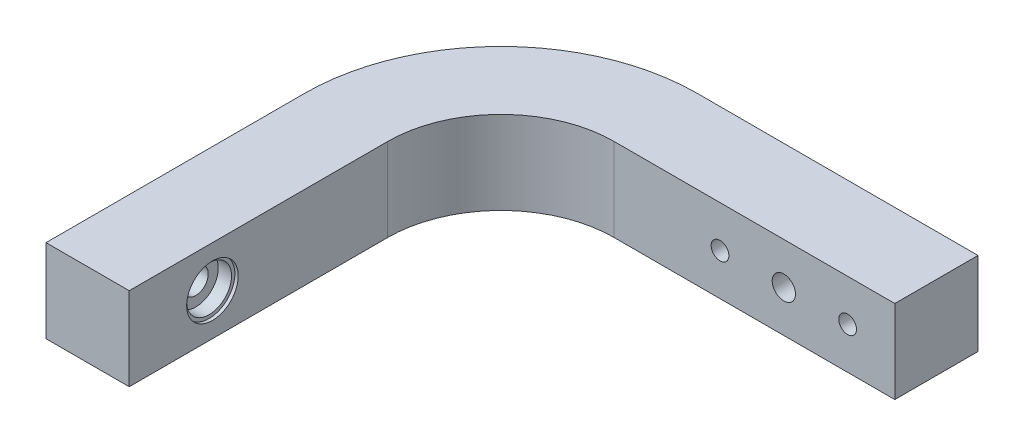
SolidWorks part; units mm, degrees
ref_plane "Front Plane" through (0, 0, 0) normal (0, 0, 1) x (1, 0, 0)
ref_plane "Top Plane" through (0, 0, 0) normal (0, 1, 0) x (1, 0, 0)
ref_plane "Right Plane" through (0, 0, 0) normal (1, 0, 0) x (0, 0, -1)
ref_axis "Z" through (0, 0, -59.2654) along (0, 0, 1)
sketch "Sketch1" plane through (0, 0, 0) normal (0, 1, 0) x (1, 0, 0)
  line L0 (-30.6, 0) -> (30.6, 0) construction
  line L1 (-66, -35.4) -> (-66, -82)
  line L2 (-66, -82) -> (-51, -82)
  line L3 (-51, -82) -> (-51, -35.4)
  line L4 (-30.6, -15) -> (30.6, -15) construction
  line L5 (0, -15) -> (0, 0) construction
  line L6 (51, -82) -> (51, -35.4) construction
  line L7 (66, -82) -> (51, -82) construction
  line L8 (66, -35.4) -> (66, -82) construction
  line L9 (30.6, 0) -> (30.6, -15) construction
  line L10 (20, -15) -> (20, 0)
  line L11 (-30.6, -15) -> (20, -15)
  line L12 (-30.6, 0) -> (20, 0)
  line L13 (0, 59.2654) -> (0, -30.9346) construction
  arc A0 (-30.6, 0) -> (-66, -35.4) centre (-30.6, -35.4) ccw
  arc A1 (-51, -35.4) -> (-30.6, -15) centre (-30.6, -35.4) cw
  arc A2 (51, -35.4) -> (30.6, -15) centre (30.6, -35.4) ccw construction
  arc A3 (30.6, 0) -> (66, -35.4) centre (30.6, -35.4) cw construction
  dimension "D3" = 20.4
  dimension "D1" = 102
  dimension "D2" = 15
  dimension "D4" = 67
  dimension "D5" = 20
extrude "Boss-Extrude1" add sketch "Sketch1" along normal blind 7.5 and the other way blind 7.5
sketch "Sketch2" plane through (-51, 0, 0) normal (-1, 0, 0) x (0, 0, 1)
  line L1 (45.1, 0) -> (-45.1, 0) construction
  line L2 (0, -8.25) -> (0, 8.25) construction
  circle A0 centre (67, 0) radius 2.25
  dimension "D1" = 4.5
  dimension "D2" = 67
extrude "Cut-Extrude1" cut sketch "Sketch2" against normal through all both and the other way through all
ref_axis "Axis2" through (-85.609, 0, 67) along (1, 0, 0)
sketch "Sketch3" plane through (0, 0, 0) normal (0, 0, -1) x (-1, 0, 0)
  line L0 (-11.5, 0) -> (11.5, 0) construction
  circle A0 centre (0, 0) radius 2.1
  circle A1 centre (-11.5, 0) radius 1.6
  circle A2 centre (11.5, 0) radius 1.6
  dimension "D1" = 4.2
  dimension "D3" = 3.2
  dimension "D2" = 23
extrude "Cut-Extrude2" cut sketch "Sketch3" against normal through all
sketch "Sketch5" plane through (0, 0, 0) normal (0, 1, 0) x (1, 0, 0)
  line L0 (-66, -71.65) -> (-65.4, -71.65)
  line L1 (-65.4, -71.65) -> (-65.4, -71.05)
  line L2 (-65.4, -71.05) -> (-63, -71.05)
  line L3 (-63, -71.05) -> (-63, -67)
  line L4 (-66, -71.65) -> (-66, -67)
  line L5 (-92.6767, -67) -> (-43.9581, -67) construction
  line L6 (-84.5878, -67) -> (-79.7197, -67) construction
  line L7 (-66, -67) -> (-63, -67)
  line L9 (-66, -35.4) -> (-66, -82) construction
  line L10 (-58.5, -78.0435) -> (-58.5, -69.815) construction
  line L11 (-66, -82) -> (-51, -82) construction
  line L12 (-51, -67) -> (-54, -67)
  line L13 (-51, -71.65) -> (-51, -67)
  line L14 (-54, -71.05) -> (-54, -67)
  line L15 (-51.6, -71.05) -> (-54, -71.05)
  line L16 (-51.6, -71.65) -> (-51.6, -71.05)
  line L17 (-51, -71.65) -> (-51.6, -71.65)
  point P8 (0, 0)
  point P14 (-58.5, -82)
  point P15 (0, 0)
  dimension "D1" = 0.6
  dimension "D2" = 4.65
  dimension "D3" = 8.1
  dimension "D4" = 3
revolve "bearing-seats" cut sketch "Sketch5" angle 360 about L6
equation "\"width\"= \"EyeDiameter\" + \"EyeClearance\""
equation "\"prongwidth\"= \"L2Thickness\""
equation "\"D2@Sketch1\"=\"prongwidth\""
equation "\"D3@Sketch1\"=\"width\"/5"
equation "\"pronglength\"= \"BasePlaneDistance\"'model implicitly adds clearance (of prongwidth) to the hole drilled at the baseplanedistance"
equation "\"D4@Sketch1\"=\"pronglength\""
equation "\"D1@Boss-Extrude1\"=\"prongwidth\"/2"
equation "\"D2@Boss-Extrude1\"=\"prongwidth\"/2"
equation "\"lbracket-plane-to-axis\"= \"BasePlaneDistance\""
equation "\"D2@Sketch2\"=\"lbracket-plane-to-axis\""
equation "\"EyeDiameter\" = 100"
equation "\"BasePlaneDistance\" = \"EyeDiameter\"/2+\"L2Thickness\"+\"EyeClearance\""
equation "\"EyeClearance\" = 2"
equation "\"D1@Sketch1\"=\"EyeDiameter\"+\"EyeClearance\""
equation "\"BearingDepth\"= 6"
equation "\"BearingHousingID\"=4.5"
equation "\"BearingFlangeThickness\"= 0.75"
equation "\"BearingFlangeOD\"=7.5"
equation "\"PrinterFilamentThickness\"= 0.1"
equation "\"ApplyPrinterOffset\"= 1'if 1, adjust hole sizes to try and make pressfits work with the 3d printer"
equation "\"L2Thickness\" = 15"
equation "\"L2_ID\" = 20"
equation "\"vx\" = 0"
equation "\"vy\" = 0"
equation "\"vz\" = 100"
equation "\"parametric_end\" = 1"
equation "\"Rw_3_xx\" = -(\"vz\")/sqr((\"vx\")^2 + (\"vz\")^2)"
equation "\"Rw_3_xy\" = 0"
equation "\"Rw_3_xz\" = (\"vx\")/sqr((\"vx\")^2 + (\"vz\")^2)"
equation "\"Rw_3_zx\" = (\"vx\")/sqr((\"vx\")^2 + (\"vy\")^2 + (\"vz\")^2)"
equation "\"Rw_3_zy\" = (\"vy\")/sqr((\"vx\")^2 + (\"vy\")^2 + (\"vz\")^2)"
equation "\"Rw_3_zz\" = (\"vz\")/sqr((\"vx\")^2 + (\"vy\")^2 + (\"vz\")^2)"
equation "\"Rw_3_yx\" = (\"vx\")*(\"vy\")/sqr((\"vx\")^4 + (\"vx\")^2*(\"vy\")^2 + 2*(\"vx\")^2*(\"vz\")^2 + (\"vy\")^2*(\"vz\")^2 + (\"vz\")^4)"
equation "\"Rw_3_yy\" = -sqr((\"vx\")^2 + (\"vz\")^2)/sqr((\"vx\")^2 + (\"vy\")^2 + (\"vz\")^2)"
equation "\"Rw_3_yz\" = (\"vy\")*(\"vz\")/sqr((\"vx\")^4 + (\"vx\")^2*(\"vy\")^2 + 2*(\"vx\")^2*(\"vz\")^2 + (\"vy\")^2*(\"vz\")^2 + (\"vz\")^4)"
equation "\"O2Targx\" = -\"BasePlaneDistance\"*(\"vx\")*(\"vy\")/sqr((\"vx\")^4 + (\"vx\")^2*(\"vy\")^2 + 2*(\"vx\")^2*(\"vz\")^2 + (\"vy\")^2*(\"vz\")^2 + (\"vz\")^4)"
equation "\"O2Targy\" = \"BasePlaneDistance\"*sqr((\"vx\")^2 + (\"vz\")^2)/sqr((\"vx\")^2 + (\"vy\")^2 + (\"vz\")^2)"
equation "\"O2Targz\" = -\"BasePlaneDistance\"*(\"vy\")*(\"vz\")/sqr((\"vx\")^4 + (\"vx\")^2*(\"vy\")^2 + 2*(\"vx\")^2*(\"vz\")^2 + (\"vy\")^2*(\"vz\")^2 + (\"vz\")^4)"
equation "\"O2Targx_0\" = -(\"BasePlaneDistance\")*sqr((\"vx\")^2 + (\"vz\")^2)/sqr((\"vx\")^2 + (\"vy\")^2 + (\"vz\")^2)"
equation "\"O2Targy_0\" = -(\"BasePlaneDistance\")*(\"vy\")*(\"vz\")/sqr((\"vx\")^4 + (\"vx\")^2*(\"vy\")^2 + 2*(\"vx\")^2*(\"vz\")^2 + (\"vy\")^2*(\"vz\")^2 + (\"vz\")^4)"
equation "\"O2Targz_0\" = (\"BasePlaneDistance\")*(\"vx\")*(\"vy\")/sqr((\"vx\")^4 + (\"vx\")^2*(\"vy\")^2 + 2*(\"vx\")^2*(\"vz\")^2 + (\"vy\")^2*(\"vz\")^2 + (\"vz\")^4) + (\"BasePlaneDistance\")"
equation "\"theta2_s1\" = arcsin(((\"BasePlaneDistance\") - (\"O2Targz_0\"))/(\"BasePlaneDistance\")) + pi"
equation "\"theta2_s2\" = -arcsin(((\"BasePlaneDistance\") - (\"O2Targz_0\"))/(\"BasePlaneDistance\"))"
equation "\"theta1_s1\" = arcsin((\"O2Targy_0\")/((\"BasePlaneDistance\")*cos((\"Theta2\")))) + pi"
equation "\"theta1_s2\" = -arcsin((\"O2Targy_0\")/((\"BasePlaneDistance\")*cos((\"Theta2\"))))"
equation "\"theta1_s3\" = -arccos(-(\"O2Targx_0\")/((\"BasePlaneDistance\")*cos((\"Theta2\")))) + 2*pi"
equation "\"theta1_s4\" = arccos(-(\"O2Targx_0\")/((\"BasePlaneDistance\")*cos((\"Theta2\"))))"
equation "\"Theta1\" = \"theta1_s2\" 'so far, theta1_s1 and theta1_s4 have agreed, and they agree with the sw constraint solver"
equation "\"Theta2\" = \"theta2_s2\""
equation "\"o2_x\" = -(\"BasePlaneDistance\")*cos((\"Theta1\"))*cos((\"Theta2\"))"
equation "\"o2_y\" = -(\"BasePlaneDistance\")*sin((\"Theta1\"))*cos((\"Theta2\"))"
equation "\"o2_z\" = (\"BasePlaneDistance\")*(sin((\"Theta2\")) + 1)"
equation "\"o1_x\" = (\"BasePlaneDistance\")*sin((\"Theta1\"))"
equation "\"o1_y\" = -(\"BasePlaneDistance\")*cos((\"Theta1\"))"
equation "\"o1_z\" = (\"BasePlaneDistance\")"
equation "\"Actuator1_Theta\" = atn(\"vx\"/\"vz\") 'ik solution for the single link joint"
equation "\"Actuator2_Theta\" = \"Theta1\"  'ik solution for the double link joint"
equation "\"MotorBaseThickness\" = 3 "
equation "\"BaseThickness\" = 3 "
equation "\"EncoderToMagnetAirgap\" = 1 'Encoder to magnet airgap"
equation "\"EncoderHeight\" = 1.192  'Height of the encoder"
equation "\"MagnetThickness\" = 0.5  'Magnet thickness"
equation "\"pcb_thickness\" = 1.6  'Thickness of the PCB"
equation "\"pcb_outer_diameter\" = 32 'the OD of the pcb"
equation "\"shaft_diameter\" = 4"
equation "\"D1@Sketch2\"=\"shaft_diameter\"*1.125"
equation "\"D2@Sketch5\"=\"ApplyPrinterOffset\" * \"PrinterFilamentThickness\" / 2 + 4.6"
equation "\"D3@Sketch5\"= \"ApplyPrinterOffset\" * \"PrinterFilamentThickness\"  + 8.00"
